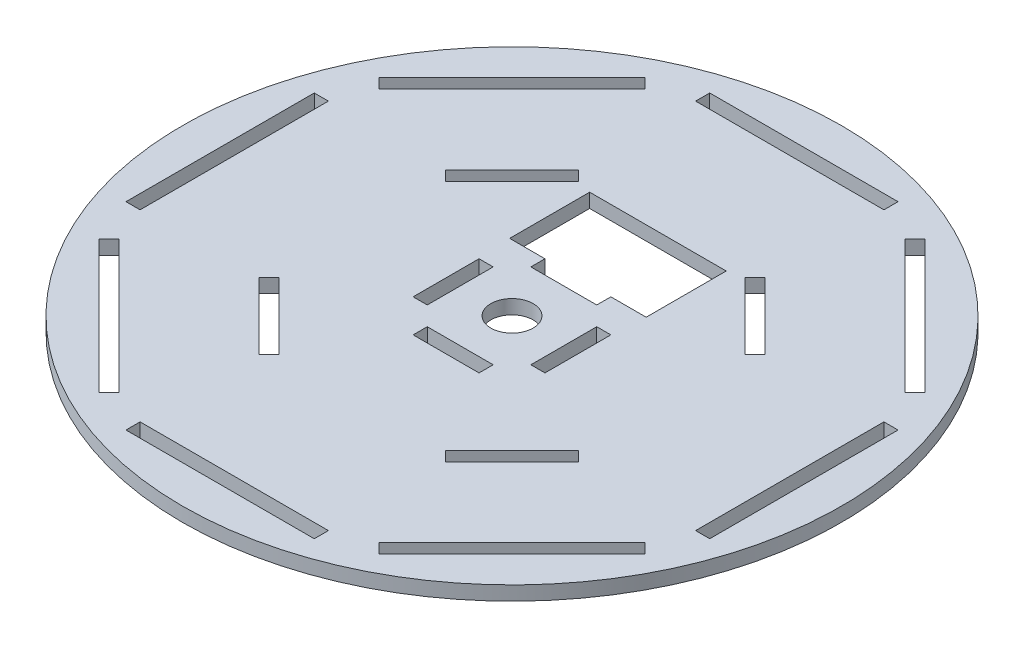
SolidWorks part; units mm, degrees
ref_plane "Alzado" through (0, 0, 0) normal (0, 0, 1) x (1, 0, 0)
ref_plane "Planta" through (0, 0, 0) normal (0, 1, 0) x (1, 0, 0)
ref_plane "Vista lateral" through (0, 0, 0) normal (1, 0, 0) x (0, 0, -1)
sketch "Croquis1" plane through (0, 0, 0) normal (0, 1, 0) x (1, 0, 0)
  line L0 (0, 11) -> (7, 11)
  line L1 (7, 11) -> (7, 14)
  line L2 (24.7487, 24.7487) -> (31.8198, 17.6777)
  line L3 (-7, 14) -> (-7, 11)
  line L4 (-7, 11) -> (0, 11)
  line L5 (11, 0) -> (11, 7)
  line L6 (11, 7) -> (14, 7)
  line L7 (14, 7) -> (14, -7)
  line L8 (14, -7) -> (11, -7)
  line L9 (11, -7) -> (11, 0)
  line L10 (0, 0) -> (-24.7487, 24.7487) construction
  line L11 (-24.7487, 24.7487) -> (-17.6777, 31.8198)
  line L12 (-17.6777, 31.8198) -> (-19.799, 33.9411)
  line L13 (-14, -7) -> (-11, -7)
  line L14 (-11, -7) -> (-11, 0)
  line L15 (-11, 0) -> (-11, 7)
  line L16 (-11, 7) -> (-14, 7)
  line L17 (-14, 7) -> (-14, -7)
  line L18 (7, -11) -> (7, -14)
  line L19 (0, -11) -> (7, -11)
  line L20 (7, -14) -> (-7, -14)
  line L21 (-7, -14) -> (-7, -11)
  line L22 (-7, -11) -> (0, -11)
  line L23 (-19.799, 33.9411) -> (-33.9411, 19.799)
  line L24 (-24.7487, 24.7487) -> (-31.8198, 17.6777)
  line L25 (-31.8198, 17.6777) -> (-33.9411, 19.799)
  line L26 (7, 14) -> (14.5, 14)
  line L27 (14.5, 14) -> (14.5, 31)
  line L28 (14.5, 31) -> (-14.5, 31)
  line L29 (-14.5, 31) -> (-14.5, 14)
  line L30 (-14.5, 14) -> (-7, 14)
  line L31 (31.8198, 17.6777) -> (33.9411, 19.799)
  line L32 (33.9411, 19.799) -> (19.799, 33.9411)
  line L33 (17.6777, 31.8198) -> (19.799, 33.9411)
  line L34 (24.7487, 24.7487) -> (17.6777, 31.8198)
  line L35 (24.7487, -24.7487) -> (17.6777, -31.8198)
  line L36 (17.6777, -31.8198) -> (19.799, -33.9411)
  line L37 (19.799, -33.9411) -> (33.9411, -19.799)
  line L38 (31.8198, -17.6777) -> (33.9411, -19.799)
  line L39 (24.7487, -24.7487) -> (31.8198, -17.6777)
  line L40 (-24.7487, -24.7487) -> (-31.8198, -17.6777)
  line L41 (0, 0) -> (0, 62) construction
  line L42 (0, 62) -> (20, 62)
  line L43 (20, 62) -> (20, 59)
  line L44 (20, 59) -> (-20, 59)
  line L45 (-20, 59) -> (-20, 62)
  line L46 (-20, 62) -> (0, 62)
  line L47 (55.8614, 27.5772) -> (27.5772, 55.8614)
  line L48 (27.5772, 55.8614) -> (29.6985, 57.9828)
  line L49 (29.6985, 57.9828) -> (43.8406, 43.8406)
  line L50 (43.8406, 43.8406) -> (57.9828, 29.6985)
  line L51 (57.9828, 29.6985) -> (55.8614, 27.5772)
  line L52 (59, -20) -> (59, 20)
  line L53 (59, 20) -> (62, 20)
  line L54 (62, 20) -> (62, 0)
  line L55 (62, 0) -> (62, -20)
  line L56 (62, -20) -> (59, -20)
  line L57 (27.5772, -55.8614) -> (55.8614, -27.5772)
  line L58 (55.8614, -27.5772) -> (57.9828, -29.6985)
  line L59 (57.9828, -29.6985) -> (43.8406, -43.8406)
  line L60 (43.8406, -43.8406) -> (29.6985, -57.9828)
  line L61 (29.6985, -57.9828) -> (27.5772, -55.8614)
  line L62 (-20, -59) -> (20, -59)
  line L63 (20, -59) -> (20, -62)
  line L64 (20, -62) -> (0, -62)
  line L65 (0, -62) -> (-20, -62)
  line L66 (-20, -62) -> (-20, -59)
  line L67 (-55.8614, -27.5772) -> (-27.5772, -55.8614)
  line L68 (-27.5772, -55.8614) -> (-29.6985, -57.9828)
  line L69 (-29.6985, -57.9828) -> (-43.8406, -43.8406)
  line L70 (-43.8406, -43.8406) -> (-57.9828, -29.6985)
  line L71 (-57.9828, -29.6985) -> (-55.8614, -27.5772)
  line L72 (-59, 20) -> (-59, -20)
  line L73 (-59, -20) -> (-62, -20)
  line L74 (-62, -20) -> (-62, 0)
  line L75 (-62, 0) -> (-62, 20)
  line L76 (-62, 20) -> (-59, 20)
  line L77 (-27.5772, 55.8614) -> (-55.8614, 27.5772)
  line L78 (-55.8614, 27.5772) -> (-57.9828, 29.6985)
  line L79 (-57.9828, 29.6985) -> (-43.8406, 43.8406)
  line L80 (-43.8406, 43.8406) -> (-29.6985, 57.9828)
  line L81 (-29.6985, 57.9828) -> (-27.5772, 55.8614)
  line L82 (-31.8198, -17.6777) -> (-33.9411, -19.799)
  line L83 (-33.9411, -19.799) -> (-19.799, -33.9411)
  line L84 (-17.6777, -31.8198) -> (-19.799, -33.9411)
  line L85 (-24.7487, -24.7487) -> (-17.6777, -31.8198)
  circle A0 centre (0, 0) radius 4.5
  circle A2 centre (0, 0) radius 70
  point P47 (0, 0)
  point P88 (0, 0)
  point P93 (0, 0)
  dimension "D1" = 9
  dimension "D2" = 14
  dimension "D3" = 140
  dimension "D4" = 7
  dimension "D5" = 3
  dimension "D6" = 14
  dimension "D7" = 35
  dimension "D8" = 3
  dimension "D9" = 10
  dimension "D10" = 3
  dimension "D11" = 20
  dimension "D12" = 10
  dimension "D14" = 62
  dimension "D15" = 20
  dimension "D16" = 3
  dimension "D17" = 40
  dimension "D19" = 17
  dimension "D13" = 4
  dimension "D20" = 29
  dimension "D21" = 3
  dimension "D18" = 8
extrude "Saliente-Extruir1" add sketch "Croquis1" along normal blind 3
